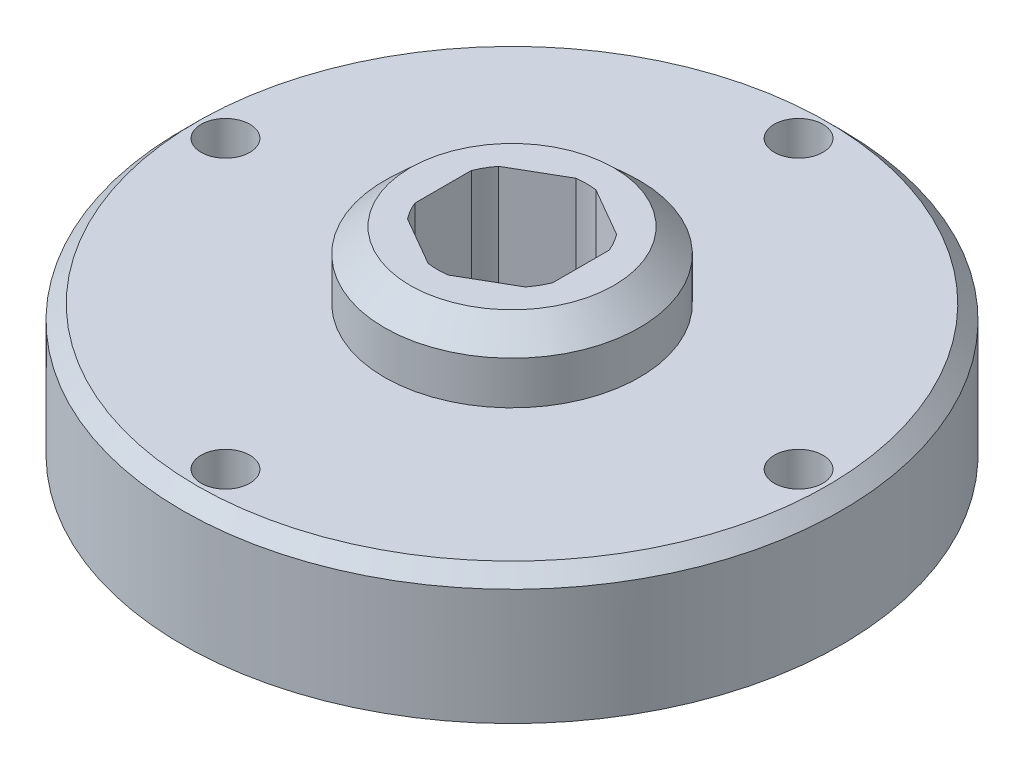
SolidWorks part; units mm, degrees
material "Nylon 6/10"
ref_plane "Front Plane" through (0, 0, 0) normal (0, 0, 1) x (1, 0, 0)
ref_plane "Top Plane" through (0, 0, 0) normal (0, 1, 0) x (1, 0, 0)
ref_plane "Right Plane" through (0, 0, 0) normal (1, 0, 0) x (0, 0, -1)
sketch "Sketch1" plane through (0, 0, 0) normal (0, 0, 1) x (1, 0, 0)
  line L0 (6.8, 0) -> (6.8, 4.953)
  line L1 (6.8, 4.953) -> (5.2, 4.953)
  line L2 (5.2, 4.953) -> (5.2, 13.7757)
  line L3 (5.2, 13.7757) -> (7.112, 13.7757)
  line L5 (8.9, 9.1132) -> (23, 9.1132)
  line L6 (23, 9.1132) -> (23, 0)
  line L7 (23, 0) -> (6.8, 0)
  line L8 (7.112, 13.7757) -> (8.9, 12.1132)
  line L9 (8.9, 12.1132) -> (8.9, 9.1132)
  line L10 (0, 0) -> (0, 16.4092) construction
  dimension "D1" = 6.8
  dimension "D2" = 23
  dimension "D3" = 4.953
  dimension "D4" = 8.9
  dimension "D5" = 4.6625
  dimension "D6" = 9.1132
  dimension "D7" = 3
  dimension "D8" = 7.112
  dimension "D9" = 5.2
revolve "Revolve1" add sketch "Sketch1" angle 360 about L10
sketch "Sketch2" plane through (0, 0, 0) normal (0, 1, 0) x (1, 0, 0)
  circle A0 centre (0, 0) radius 20 construction
  point P3 (-20, 0)
  dimension "D1" = 40
hole_wizard "M3 Clearance Hole1" positions "Sketch2" profile "Sketch3" hole size "M3" standard "ANSI Metric" end condition through all
sketch "Sketch3" plane through (-20, 0, 0) normal (1, 0, 0) x (0, 0, -1)
  line L0 (0, 0) -> (0, 13.7757)
  line L1 (0, 13.7757) -> (1.7, 13.7757)
  line L2 (1.7, 13.7757) -> (1.7, 0)
  line L5 (1.7, 0) -> (0, 0)
  line L11 (0, -6.35) -> (0, 107.95) construction
  dimension "Thru Hole Dia." = 3.4
  dimension "Thru Hole Depth" = 13.7757
pattern_circular "CirPattern1" count 4 over 360 about axis through (0, 0, 0) along (0, -1, 0) of "M3 Clearance Hole1"
sketch "Sketch4" plane through (0, 4.953, 0) normal (0, -1, 0) x (1, 0, 0)
  line L1 (4.8125, 2.7785) -> (0, 5.557)
  line L2 (0, 5.557) -> (-4.8125, 2.7785)
  line L3 (-4.8125, 2.7785) -> (-4.8125, -2.7785)
  line L4 (-4.8125, -2.7785) -> (0, -5.557)
  line L5 (0, -5.557) -> (4.8125, -2.7785)
  line L6 (4.8125, -2.7785) -> (4.8125, 2.7785)
  circle A0 centre (0, 0) radius 4.8125 construction
  circle A1 centre (0, 0) radius 5.2 construction
  circle A2 centre (0, 0) radius 5.2
  circle M9 centre (0, 0) radius 5.2
  dimension "D1" = 9.625
extrude "Boss-Extrude1" add sketch "Sketch4" against normal up to surface (8.8227 mm away) contours L2 M9 | L3 M9 | L4 M9 | L5 M9 | L6 M9 | L1 M9 region at (2.484, 4.953, 4.3024) region at (4.968, 4.953, 0) region at (-2.484, 4.953, 4.3024) region at (2.484, 4.953, -4.3024) region at (-4.968, 4.953, 0) region at (-2.484, 4.953, -4.3024) up to face at (0, 13.7757, -5.2)
chamfer "Chamfer1" distance 0.75 angle 45 1 edges at (0, 0, -6.8)
chamfer "Chamfer2" distance 1 angle 45 1 edges at (0, 9.1132, -23)
